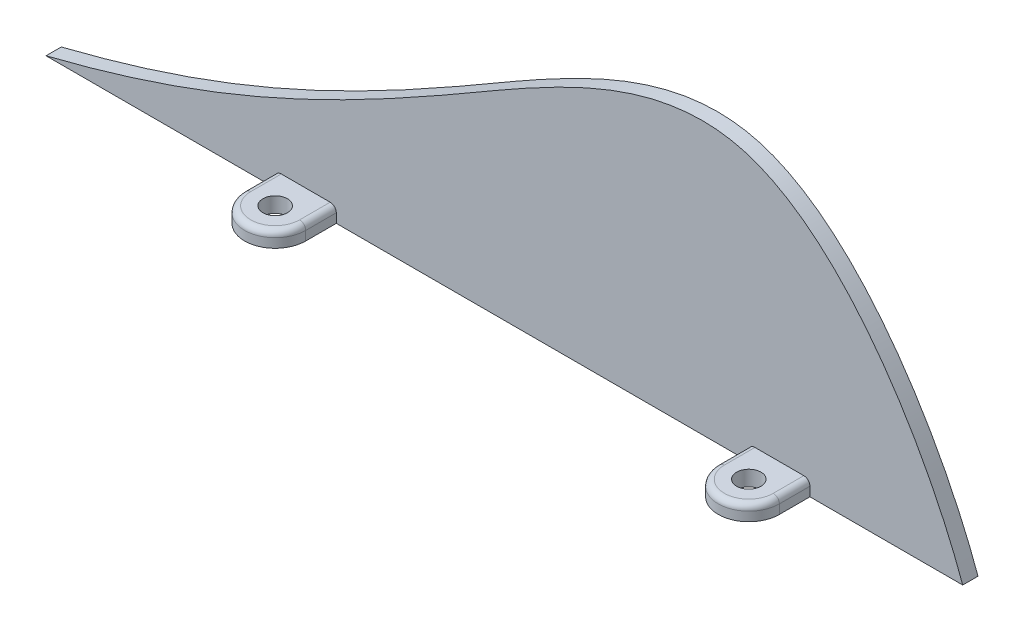
SolidWorks part; units mm, degrees
ref_plane "前视基准面" through (0, 0, 0) normal (0, 0, 1) x (1, 0, 0)
ref_plane "上视基准面" through (0, 0, 0) normal (0, 1, 0) x (1, 0, 0)
ref_plane "右视基准面" through (0, 0, 0) normal (1, 0, 0) x (0, 0, -1)
sketch "草图1" plane through (0, 0, 0) normal (0, 0, 1) x (1, 0, 0)
  line L1 (-60, 17.5) -> (60, 17.5)
  line L2 (-60, 17.5) -> (-60, -17.5)
  line L3 (-60, -17.5) -> (60, -17.5)
  line L4 (60, 17.5) -> (60, -17.5)
  line L5 (-60, 17.5) -> (60, -17.5) construction
  line L6 (-60, -17.5) -> (60, 17.5) construction
  spline S0 degree 3 poles (-60, -17.5) (-39.16, -12.2934) (-14.3091, -0.6983) (35.2794, 30.576) (55.7556, -5.6312) (60, -17.5) knots 0 0 0 0 0.404703 0.677893 1 1 1 1
  point P0 (0, 0)
  point P1 (-26.2859, 0)
  point P7 (0, 0)
  point P9 (0, 0)
  point P11 (11.7103, 10.2856)
  point P13 (20.5643, 5.5138)
  point P14 (-8.5399, 10.8512)
  point P15 (0, 0)
  point P16 (33.3569, 10.2624)
  point P18 (47.5698, -9.2871)
  point P19 (-23.7367, -6.3602)
  point P20 (-4.7559, 7.477)
  point P21 (17.5789, 17.5)
  point P22 (-19.3717, -8.972)
  point P23 (-1.9885, 4.024)
  point P24 (49.6631, -8.0734)
  point P25 (20.524, 17.5)
  point P26 (23.2092, 17.5)
  point P27 (50.1887, 1.5)
  point P28 (-6.3641, 4.9747)
  point P29 (-27.1448, -5.9733)
  point P30 (30.9491, 17.5)
  dimension "D1" = 35
  dimension "D2" = 120
extrude "凸台-拉伸2" add sketch "草图1" along normal blind 2 contours S0 L3 L1 | S0 L1 region at (25.7473, 17.7472, 0) region at (13.4949, -4.2759, 0)
ref_plane "镜像面" through (0, 0, 1) normal (0, 0, 1) x (1, 0, 0)
sketch "草图2" plane through (0, 0, 2) normal (0, 0, 1) x (1, 0, 0)
  line L0 (-60, -17.5) -> (60, -17.5) construction
  line L1 (40, -17.5) -> (32, -17.5)
  line L2 (40, -17.5) -> (40, -15.5)
  line L3 (40, -15.5) -> (32, -15.5)
  line L4 (32, -17.5) -> (32, -15.5)
  line L5 (-22, -17.5) -> (-30, -17.5)
  line L6 (-22, -17.5) -> (-22, -15.5)
  line L7 (-22, -15.5) -> (-30, -15.5)
  line L8 (-30, -17.5) -> (-30, -15.5)
  dimension "D1" = 2
  dimension "D2" = 2
  dimension "D3" = 8
  dimension "D4" = 8
  dimension "D5" = 20
  dimension "D6" = 30
extrude "凸台-拉伸3" add sketch "草图2" along normal blind 8
ref_plane "基准面4" through (-26, 0, 0) normal (-1, 0, 0) x (0, 0, 1)
ref_plane "基准面5" through (0, 0, 6) normal (0, 0, 1) x (1, 0, 0)
ref_plane "基准面6" through (36, 0, 0) normal (-1, 0, 0) x (0, 0, 1)
hole_wizard "M3 间隙孔1" positions "草图3" profile "草图4" hole size "M3" standard "ISO" end condition up to next
sketch "草图3" plane through (0, -15.5, 0) normal (0, 1, 0) x (1, 0, 0)
  line L2 (-26, 0.55) -> (-26, -0.55) construction
  line L3 (-20.0756, -6) -> (20.0756, -6) construction
  line L4 (36, 0.55) -> (36, -0.55) construction
  point P0 (-26, -6)
  point P2 (36, -6)
  point P5 (0, 0)
  point P6 (0, 0)
  point P9 (0, 0)
  point P12 (0, 0)
  point P13 (0, 0)
  point P16 (0, 0)
  point P19 (0, 0)
  point P20 (0, 0)
sketch "草图4" plane through (-26, -15.5, 6) normal (1, 0, 0) x (0, 0, 1)
  line L0 (0, 0) -> (0, 2)
  line L1 (0, 2) -> (1.6, 2)
  line L2 (1.6, 2) -> (1.6, 0)
  line L5 (1.6, 0) -> (0, 0)
  line L11 (0, -6.35) -> (0, 107.95) construction
  dimension "通孔孔直径" = 3.2
  dimension "通孔孔深度" = 2
fillet "圆角1" 2 edges at (-30, -16.5, 10) (-22, -16.5, 10) type full round first side face at (-30, -16.5, 6) second side face at (-22, -16.5, 6) middle face at (-26, -16.5, 10)
fillet "圆角2" 2 edges at (32, -16.5, 10) (40, -16.5, 10) type full round first side face at (32, -16.5, 6) second side face at (40, -16.5, 6) middle face at (36, -16.5, 10)
mirror "镜向2" about plane through (0, 0, 1) normal (0, 0, 1) of "圆角1", "凸台-拉伸3", "M3 间隙孔1", "圆角2"
fillet "圆角3" radius 0.8 12 edges at (-30, -15.5, 4) (-22, -15.5, 4) (-26, -15.5, 10) (32, -15.5, 4) (40, -15.5, 4) (36, -15.5, 10) (40, -15.5, -2) (32, -15.5, -2) (-22, -15.5, -2) (-30, -15.5, -2) (36, -15.5, -8) (-26, -15.5, -8)
